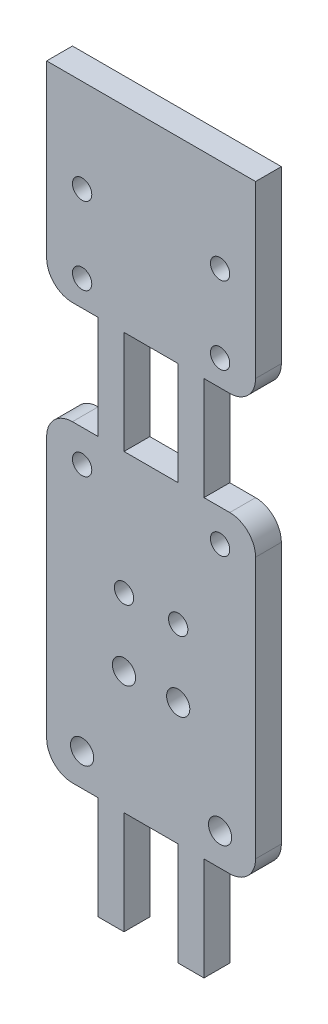
SolidWorks part; units mm, degrees
ref_plane "Front Plane" through (0, 0, 0) normal (0, 0, 1) x (1, 0, 0)
ref_plane "Top Plane" through (0, 0, 0) normal (0, 1, 0) x (1, 0, 0)
ref_plane "Right Plane" through (0, 0, 0) normal (1, 0, 0) x (0, 0, -1)
sketch "Sketch1" plane through (0, 0, 0) normal (0, 0, 1) x (1, 0, 0)
  line L0 (4, 44.7) -> (4, 52.7)
  line L1 (0, -0.06) -> (16.2, -0.06) construction
  line L2 (8.1, -0.06) -> (8.1, 67.93) construction
  line L3 (6, 12.44) -> (10.2, 12.44) construction
  line L4 (6, 20.44) -> (10.2, 20.44)
  line L5 (6, 44.7) -> (6, 52.7)
  line L6 (0, 54.7) -> (0, 67.93)
  line L7 (6, 44.7) -> (10.2, 44.7)
  line L8 (6, 52.7) -> (10.2, 52.7)
  line L9 (2, 44.7) -> (4, 44.7)
  line L10 (0, 67.93) -> (16.2, 67.93)
  line L11 (2, 20.44) -> (4, 20.44)
  line L12 (0, 22.44) -> (0, 42.7)
  line L13 (16.2, 12.44) -> (12.2, 12.44) construction
  line L14 (12.2, 20.44) -> (12.2, 12.44)
  line L15 (10.2, 12.44) -> (10.2, 20.44)
  line L16 (16.2, 12.44) -> (16.2, -0.06) construction
  line L17 (14.2, 52.7) -> (12.2, 52.7)
  line L18 (16.2, 22.44) -> (16.2, 42.7)
  line L19 (14.2, 20.44) -> (12.2, 20.44)
  line L20 (14.2, 44.7) -> (12.2, 44.7)
  line L21 (16.2, 54.7) -> (16.2, 67.93)
  line L22 (10.2, 44.7) -> (10.2, 52.7)
  line L23 (12.2, 44.7) -> (12.2, 52.7)
  line L24 (4, 12.44) -> (6, 12.44)
  line L25 (10.2, 12.44) -> (12.2, 12.44)
  line L36 (2, 52.7) -> (4, 52.7)
  line L46 (0, 12.44) -> (0, -0.06) construction
  line L47 (6, 12.44) -> (6, 20.44)
  line L48 (4, 20.44) -> (4, 12.44)
  line L49 (0, 12.44) -> (4, 12.44) construction
  circle A0 centre (2.75, 60.7) radius 0.75
  circle A1 centre (13.35, 9.94) radius 0.9 construction
  circle A2 centre (13.35, 3.94) radius 0.9 construction
  circle A3 centre (13.45, 54.7) radius 0.75
  arc A4 (16.2, 54.7) -> (14.2, 52.7) centre (14.2, 54.7) cw
  circle A5 centre (13.45, 42.2) radius 0.75
  circle A6 centre (13.45, 22.94) radius 0.9
  circle A7 centre (10.2, 29.94) radius 0.9
  arc A8 (16.2, 22.44) -> (14.2, 20.44) centre (14.2, 22.44) cw
  circle A9 centre (6, 35.2) radius 0.75
  arc A10 (14.2, 44.7) -> (16.2, 42.7) centre (14.2, 42.7) cw
  circle A11 centre (13.45, 60.7) radius 0.75
  circle A12 centre (10.2, 35.2) radius 0.75
  arc A27 (2, 44.7) -> (0, 42.7) centre (2, 42.7) ccw
  arc A31 (0, 22.44) -> (2, 20.44) centre (2, 22.44) ccw
  circle A33 centre (6, 29.94) radius 0.9
  circle A35 centre (2.75, 22.94) radius 0.9
  circle A37 centre (2.75, 42.2) radius 0.75
  arc A43 (0, 54.7) -> (2, 52.7) centre (2, 54.7) ccw
  circle A45 centre (2.75, 54.7) radius 0.75
  circle A46 centre (2.85, 3.94) radius 0.9 construction
  circle A47 centre (2.85, 9.94) radius 0.9 construction
  point P30 (8.1, 20.44)
  point P31 (8.1, 12.44)
  point P47 (8.1, 52.7)
  point P48 (8.1, 44.7)
  dimension "D10" = 1.8
  dimension "D11" = 2
  dimension "D18" = 2
  dimension "D26" = 2
  dimension "D1" = 8
  dimension "D2" = 8
  dimension "D3" = 4
  dimension "D4" = 6
  dimension "D5" = 2.5
  dimension "D6" = 4
  dimension "D9" = 2
  dimension "D12" = 2.5
  dimension "D14" = 9.5
  dimension "D16" = 2
  dimension "D17" = 2
  dimension "D19" = 2.5
  dimension "D21" = 2
  dimension "D22" = 2
  dimension "D27" = 2
  dimension "D29" = 2
  dimension "D7" = 2.85
  dimension "D8" = 2.85
  dimension "D13" = 2.75
  dimension "D15" = 6
  dimension "D20" = 2.75
  dimension "D23" = 2.75
  dimension "D28" = 6
  dimension "D30" = 2.75
  dimension "D31" = 8.1
  dimension "D32" = 15.23
  dimension "D24" = 24.26
  dimension "D25" = 9.5
  dimension "D33" = 6
extrude "Boss-Extrude1" add sketch "Sketch1" along normal blind 2
sketch "Sketch2" plane through (0, 0, 2) normal (0, 0, 1) x (1, 0, 0)
  line L0 (12.2, 12.44) -> (4, 12.44)
  line L1 (4, 20.44) -> (12.2, 20.44)
  line L2 (12.2, 20.44) -> (12.2, 12.44)
  line L3 (4, 12.44) -> (4, 20.44)
  line L4 (4, 52.7) -> (12.2, 52.7)
  line L5 (12.2, 52.7) -> (12.2, 44.7)
  line L6 (12.2, 44.7) -> (4, 44.7)
  line L7 (4, 44.7) -> (4, 52.7)
extrude "Cut-Extrude1" [suppressed] cut sketch "Sketch2" against normal up to surface (2 mm away) up to face at (3.5, 42.2, 0)
equation "\"D24@Sketch1\"= \"HL@parametersSketch@prostheticParameters.SLDPRT\" * 0.196 - 4 - 8'Thumb PIP Length"
equation "\"D32@Sketch1\" = \"HL@parametersSketch@prostheticParameters.SLDPRT\" * 0.158 - 4 - 10'Thumb DIP Length - Gap Fingertip"
equation "\"D31@Sketch1\"= \"fingerWidth@parametersSketch@prostheticParameters.SLDPRT\" / 2'Finger Width"
equation "\"D10@Sketch1\"= 1.5 + \"tol1@parametersSketch@prostheticParameters.SLDPRT\""
